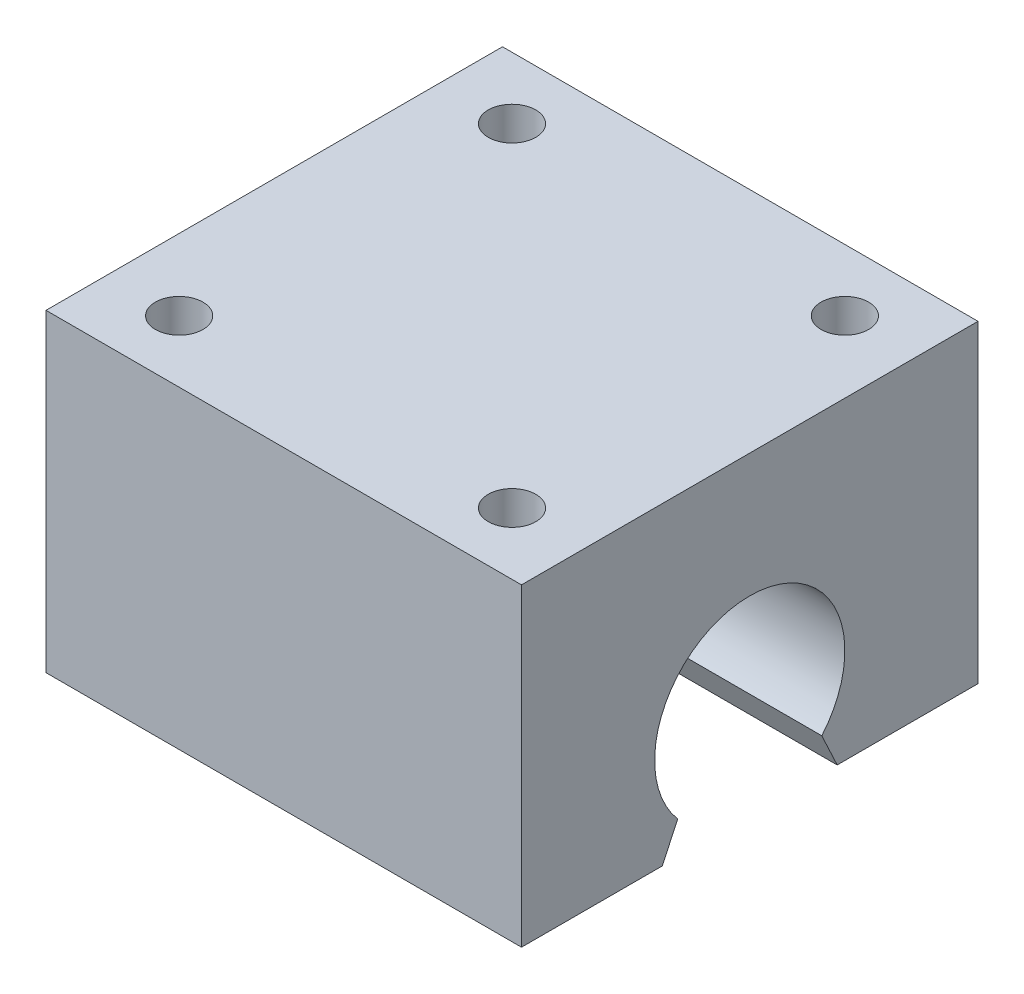
SolidWorks part; units mm, degrees
ref_plane "Front Plane" through (0, 0, 0) normal (0, 0, 1) x (1, 0, 0)
ref_plane "Top Plane" through (0, 0, 0) normal (0, 1, 0) x (1, 0, 0)
ref_plane "Right Plane" through (0, 0, 0) normal (1, 0, 0) x (0, 0, -1)
sketch "Sketch1" plane through (0, 0, 0) normal (1, 0, 0) x (0, 0, -1)
  line L0 (0, -6.5) -> (0, 0) construction
  line L1 (24, -16.5) -> (9.1941, -16.5)
  line L2 (24, -16.5) -> (24, 16.5)
  line L3 (24, 16.5) -> (-24, 16.5)
  line L4 (-24, -16.5) -> (-24, 16.5)
  line L5 (24, -16.5) -> (-24, 16.5) construction
  line L6 (24, 16.5) -> (-24, -16.5) construction
  line L7 (-7.5751, -13.0282) -> (-9.1941, -16.5)
  line L8 (-9.1941, -16.5) -> (-24, -16.5)
  line L9 (9.1941, -16.5) -> (7.5751, -13.0282)
  line L10 (0, 0) -> (0, -6.5) construction
  line L11 (-9.1941, -16.5) -> (0, -16.5) construction
  line L12 (0, -16.5) -> (9.1941, -16.5) construction
  arc A0 (7.5751, -13.0282) -> (-7.5751, -13.0282) centre (0, -6.5) ccw
  point P0 (0, 0)
  dimension "D6" = 10
  dimension "D1" = 33
  dimension "D2" = 48
  dimension "D3" = 23
  dimension "D4" = 25
  dimension "D5" = 25
extrude "Boss-Extrude1" add sketch "Sketch1" along normal blind 50
sketch "Sketch2" plane through (0, 16.5, 0) normal (0, 1, 0) x (1, 0, 0)
  line L0 (0, 24) -> (50, -24) construction
  line L1 (50, -24) -> (50, 24) construction
  line L4 (42.5, -17.5) -> (7.5, -17.5) construction
  line L5 (42.5, -17.5) -> (42.5, 17.5) construction
  line L6 (42.5, 17.5) -> (7.5, 17.5) construction
  line L7 (7.5, -17.5) -> (7.5, 17.5) construction
  line L8 (42.5, -17.5) -> (7.5, 17.5) construction
  line L9 (42.5, 17.5) -> (7.5, -17.5) construction
  circle A0 centre (7.5, 17.5) radius 2.5
  circle A1 centre (42.5, 17.5) radius 2.5
  circle A2 centre (42.5, -17.5) radius 2.5
  circle A3 centre (7.5, -17.5) radius 2.5
  point P4 (25, 0)
  point P9 (25, 0)
  dimension "D1" = 5
  dimension "D2" = 35
  dimension "D3" = 35
extrude "Cut-Extrude1" cut sketch "Sketch2" against normal blind 5
ref_axis "Axis1" through (7.5, 11.5, -17.5) along (0, 1, 0)
ref_axis "Axis2" through (42.5, 11.5, -17.5) along (0, 1, 0)
ref_axis "Axis3" through (42.5, 11.5, 17.5) along (0, 1, 0)
ref_axis "Axis4" through (7.5, 11.5, 17.5) along (0, 1, 0)
